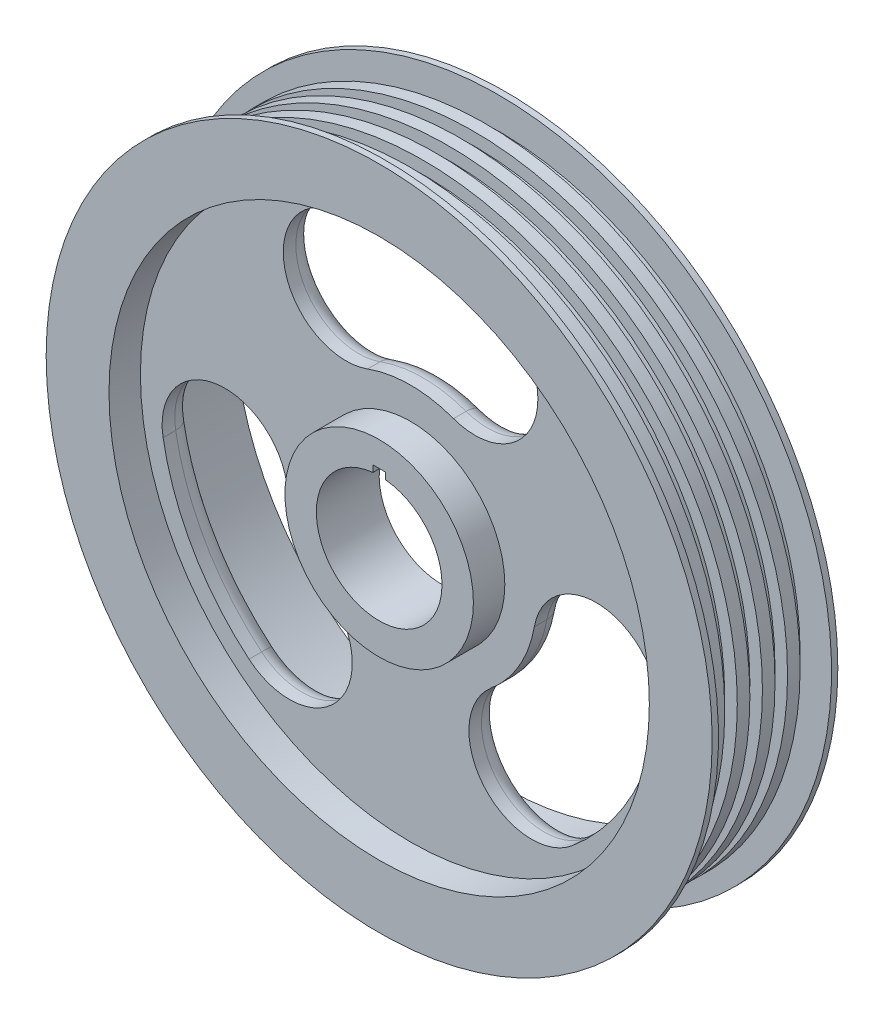
SolidWorks part; units mm, degrees
ref_plane "Front Plane" through (0, 0, 0) normal (0, 0, 1) x (1, 0, 0)
ref_plane "Top Plane" through (0, 0, 0) normal (0, 1, 0) x (1, 0, 0)
ref_plane "Right Plane" through (0, 0, 0) normal (1, 0, 0) x (0, 0, -1)
sketch "Sketch1" plane through (0, 0, 0) normal (0, 0, 1) x (1, 0, 0)
  circle A0 centre (0, 0) radius 53
  dimension "D1" = 106
extrude "Boss-Extrude1" add sketch "Sketch1" along normal blind 20
shell "Shell1" thickness 10
sketch "Sketch2" plane through (0, 0, 10) normal (0, 0, -1) x (-1, 0, 0)
  circle A0 centre (0, 0) radius 10
  dimension "D1" = 20
extrude "Cut-Extrude1" cut sketch "Sketch2" against normal blind 20
sketch "Sketch3" plane through (0, 0, 0) normal (0, 1, 0) x (1, 0, 0)
  line L0 (53, -20) -> (53, 0) construction
  line L1 (53, -1) -> (50, -1)
  line L2 (53, -1) -> (53, -19)
  line L3 (53, -19) -> (50, -19)
  line L4 (50, -1) -> (50, -19)
  line L5 (53, 0) -> (-53, 0) construction
  line L6 (-53, -20) -> (53, -20) construction
  line L7 (0, 0) -> (0, -22.9203) construction
  dimension "D1" = 1
  dimension "D2" = 1
  dimension "D3" = 3
revolve "Cut-Revolve1" cut sketch "Sketch3" angle 360 about L7
sketch "Sketch4" plane through (0, 0, 0) normal (0, 1, 0) x (1, 0, 0)
  line L0 (-50, -1) -> (50, -1) construction
  line L1 (48, -1) -> (50, -1)
  line L2 (48, -1) -> (48, -3)
  line L3 (48, -3) -> (50, -3)
  line L4 (50, -1) -> (50, -3)
  line L5 (50, -19) -> (50, -1) construction
  dimension "D1" = 2
  dimension "D2" = 2
revolve "Cut-Revolve2" cut sketch "Sketch4" angle 360 about axis through (0, 0, 20) along (0, 0, -1)
pattern_linear "LPattern1" count 5 spacing 4 along (0, 0, 1) of "Cut-Revolve2"
sketch "Sketch5" plane through (0, 0, 10) normal (0, 0, -1) x (-1, 0, 0)
  line L0 (0, 0) -> (0, 22.2562) construction
  line L5 (-1, 11) -> (1, 11)
  line L6 (-1, 11) -> (-1, 8)
  line L7 (-1, 8) -> (1, 8)
  line L8 (1, 11) -> (1, 8)
  line L9 (-1, 11) -> (1, 8) construction
  line L10 (-1, 8) -> (1, 11) construction
  point P0 (0, 9.5)
  dimension "D1" = 90
  dimension "D2" = 3
  dimension "D3" = 2
  dimension "D4" = 11
extrude "Cut-Extrude2" cut sketch "Sketch5" against normal blind 20
sketch "Sketch6" plane through (0, 0, 20) normal (0, 0, 1) x (1, 0, 0)
  circle A0 centre (0, 0) radius 43 construction
  circle A1 centre (0, 0) radius 43
  circle A2 centre (0, 0) radius 15
  dimension "D1" = 30
extrude "Cut-Extrude3" cut sketch "Sketch6" against normal blind 5
sketch "Sketch7" plane through (0, 0, 10) normal (0, 0, -1) x (-1, 0, 0)
  line L0 (0, 0) -> (0, 60.9673) construction
  line L1 (-10.2606, 28.1908) -> (0, 0) construction
  line L2 (0, 0) -> (10.2606, 28.1908) construction
  arc A0 (-10.2606, 28.1908) -> (10.2606, 28.1908) centre (0, 0) cw construction
  arc A1 (13.6808, 37.5877) -> (-13.6808, 37.5877) centre (0, 0) ccw
  arc A2 (6.8404, 18.7939) -> (-6.8404, 18.7939) centre (0, 0) ccw
  arc A3 (6.8404, 18.7939) -> (13.6808, 37.5877) centre (10.2606, 28.1908) ccw
  arc A4 (-13.6808, 37.5877) -> (-6.8404, 18.7939) centre (-10.2606, 28.1908) ccw
  point P4 (0, 30)
  dimension "D2" = 10
  dimension "D3" = 30
  dimension "D1" = 20
extrude "Cut-Extrude4" cut sketch "Sketch7" against normal blind 5
pattern_circular "CirPattern1" count 3 over 360 about axis through (0, 0, 0) along (0, 0, 1) of "Cut-Extrude4"
fillet "Fillet1" radius 3 12 edges at (-31.2807, 4.6386, 10) (-34.641, -20, 10) (-11.6232, -29.4092, 10) (11.6232, -29.4092, 10) (34.641, -20, 10) (31.2807, 4.6386, 10) (0, 20, 10) (19.6575, 24.7706, 10) (0, 40, 10) (-17.3205, -10, 10) (17.3205, -10, 10) (-19.6575, 24.7706, 10)
